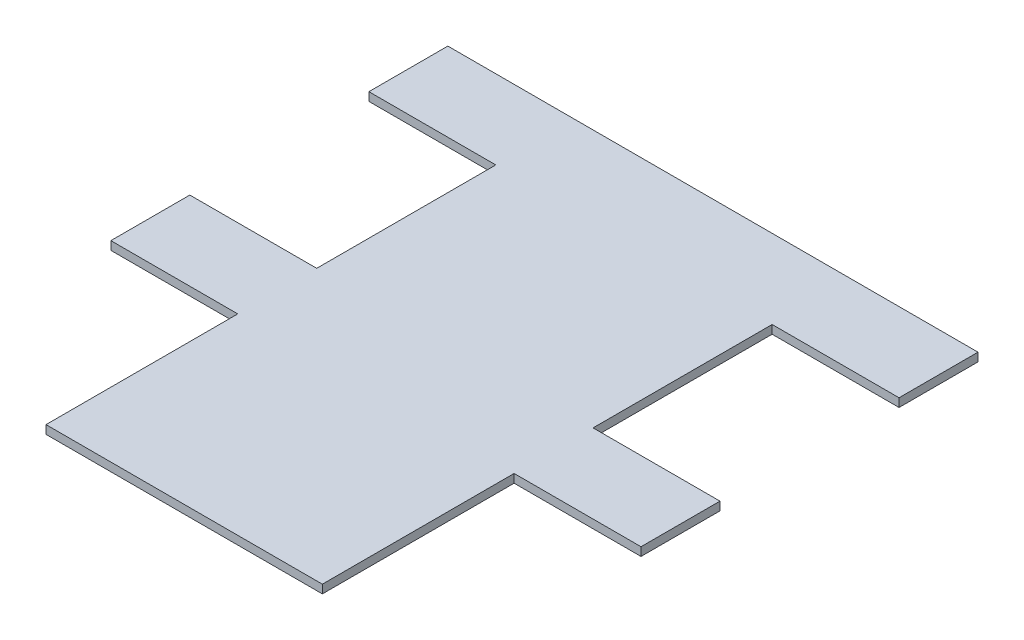
SolidWorks part; units mm, degrees
ref_plane "Front Plane" through (0, 0, 0) normal (0, 0, 1) x (1, 0, 0)
ref_plane "Top Plane" through (0, 0, 0) normal (0, 1, 0) x (1, 0, 0)
ref_plane "Right Plane" through (0, 0, 0) normal (1, 0, 0) x (0, 0, -1)
sketch "Sketch2" plane through (0, 0, 0) normal (0, 1, 0) x (1, 0, 0)
  line L0 (-22.5, 93.75) -> (-22.5, 79.75)
  line L1 (-22.5, 79.75) -> (0, 79.75)
  line L2 (0, 79.75) -> (0, 48)
  line L3 (0, 48) -> (-22.5, 48)
  line L4 (-22.5, 48) -> (-22.5, 34)
  line L5 (-22.5, 34) -> (0, 34)
  line L6 (0, 34) -> (0, 0)
  line L8 (49, 0) -> (49, 34)
  line L9 (49, 34) -> (71.5, 34)
  line L10 (71.5, 34) -> (71.5, 48)
  line L11 (71.5, 48) -> (49, 48)
  line L12 (49, 48) -> (49, 79.75)
  line L13 (49, 79.75) -> (71.5, 79.75)
  line L14 (71.5, 79.75) -> (71.5, 93.75)
  line L15 (71.5, 93.75) -> (-22.5, 93.75)
  line L17 (0, 0) -> (49, 0)
  dimension "D1" = 14
  dimension "D2" = 31.75
  dimension "D3" = 14
  dimension "D4" = 93.75
  dimension "D5" = 94
  dimension "D6" = 49
extrude "Boss-Extrude1" add sketch "Sketch2" along normal blind 1.5
